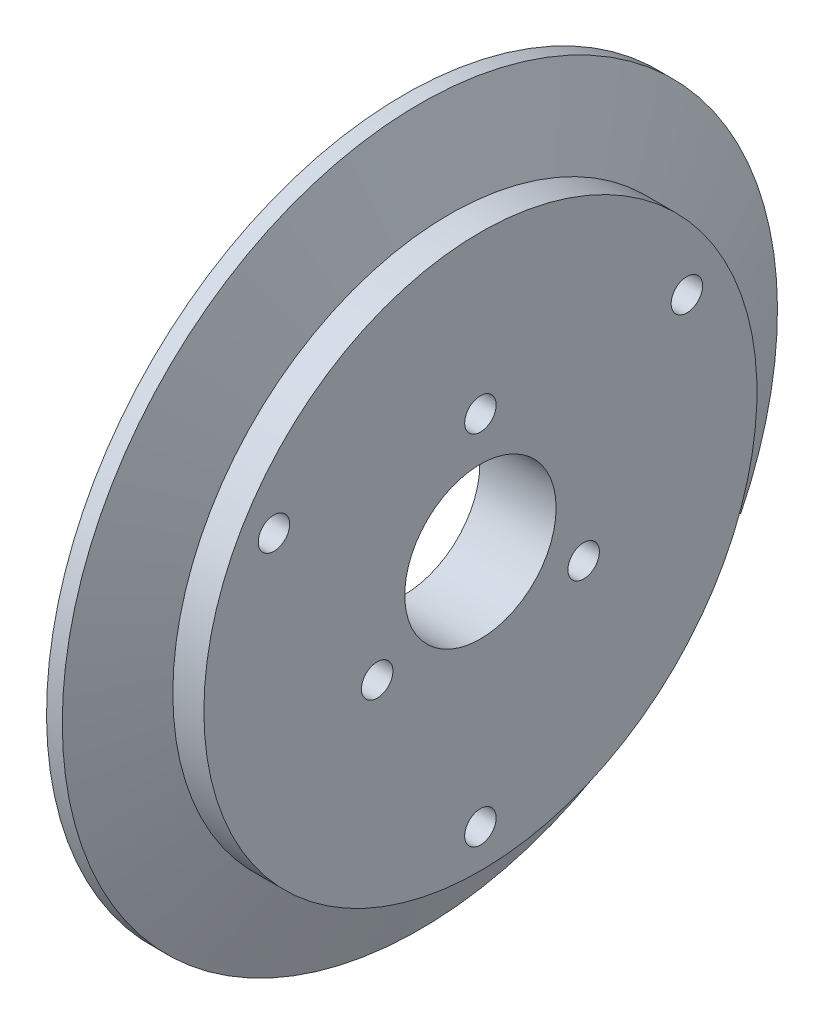
SolidWorks part; units mm, degrees
ref_plane "Front Plane" through (0, 0, 0) normal (0, 0, 1) x (1, 0, 0)
ref_plane "Top Plane" through (0, 0, 0) normal (0, 1, 0) x (1, 0, 0)
ref_plane "Right Plane" through (0, 0, 0) normal (1, 0, 0) x (0, 0, -1)
sketch "Sketch3" plane through (0, 0, 0) normal (0, 0, 1) x (1, 0, 0)
  line L1 (0, 0) -> (8, 0)
  line L2 (0, 0) -> (0, 37.5)
  line L3 (0, 37.5) -> (1.65, 37.5)
  line L5 (8, 120) -> (8, 104.2471) construction
  line L6 (8, 29) -> (4.7437, 29)
  line L8 (1.65, 37.5) -> (4.7437, 29)
  line L9 (8, 29) -> (8, 0)
  point P11 (8, 29)
  dimension "D1" = 8
  dimension "D2" = 37.5
  dimension "D3" = 6.35
  dimension "D4" = 20
  dimension "D5" = 8.5
  dimension "D6" = 1.65
revolve "Revolve1" add sketch "Sketch3" angle 360 about L1
ref_plane "Plane1" through (0, -19, 0) normal (0, 1, 0) x (1, 0, 0)
sketch "Sketch5" plane through (0, 0, 0) normal (1, 0, 0) x (0, 0, -1)
  circle A0 centre (0, 0) radius 7.94
  dimension "D1" = 15.88
extrude "Cut-Extrude1" cut sketch "Sketch5" along normal through all
sketch "Sketch7" plane through (8, 0, 0) normal (1, 0, 0) x (0, 0, -1)
  line L0 (0, 0) -> (0, 60) construction
  line L1 (0, 0) -> (46.5572, -26.8798) construction
  line L2 (0, 0) -> (-46.7349, -26.9824) construction
  line L3 (0, 0) -> (-51.719, 29.86) construction
  line L4 (0, 0) -> (51.3935, 29.6721) construction
  line L5 (0, 0) -> (0, -46.0855) construction
  circle A0 centre (0, 0) radius 12.5 construction
  circle A1 centre (0, 0) radius 25 construction
  circle A2 centre (0, 12.5) radius 1.65
  circle A3 centre (-10.8253, -6.25) radius 1.65
  circle A4 centre (10.8253, -6.25) radius 1.65
  circle A5 centre (-21.6506, 12.5) radius 1.65
  circle A6 centre (21.6506, 12.5) radius 1.65
  circle A7 centre (0, -25) radius 1.65
  dimension "D3" = 25
  dimension "D4" = 50
  dimension "D5" = 3.3
  dimension "D6" = 3.3
  dimension "D7" = 3.3
  dimension "D8" = 3.3
  dimension "D9" = 3.3
  dimension "D10" = 3.3
  dimension "D1" = 120
  dimension "D2" = 120
  dimension "D11" = 60
  dimension "D12" = 60
extrude "Cut-Extrude3" cut sketch "Sketch7" against normal through all
ref_axis "Axis1" through (8, 0, 0) along (-1, 0, 0)
ref_plane "Plane2" through (0, 0, 0) normal (0, 0.5, 0.866) x (1, 0, 0)
ref_plane "Plane3" through (0, -10, -17.3205) normal (0, 0.5, 0.866) x (1, 0, 0)
sketch "Sketch6" plane through (0, -38.5, -0.866) normal (0, -0.5, -0.866) x (1, 0, 0)
  line L0 (0, 4.591) -> (0, -70.409) construction
  line L1 (0, -30.409) -> (2, -30.409)
  line L2 (0, -30.409) -> (0, -35.409)
  line L3 (0, -35.409) -> (2, -35.409)
  line L4 (2, -30.409) -> (2, -35.409)
  line L5 (0, -32.909) -> (6.7273, -32.909) construction
  dimension "D1" = 5
  dimension "D2" = 2
extrude "Cut-Extrude2" cut sketch "Sketch6" along normal blind 65.4
equation "\"D10@Sketch7\"=\"D5@Sketch7\""
equation "\"D9@Sketch7\"=\"D5@Sketch7\""
equation "\"D8@Sketch7\"=\"D5@Sketch7\""
equation "\"D7@Sketch7\"=\"D5@Sketch7\""
equation "\"D6@Sketch7\"=\"D5@Sketch7\""
